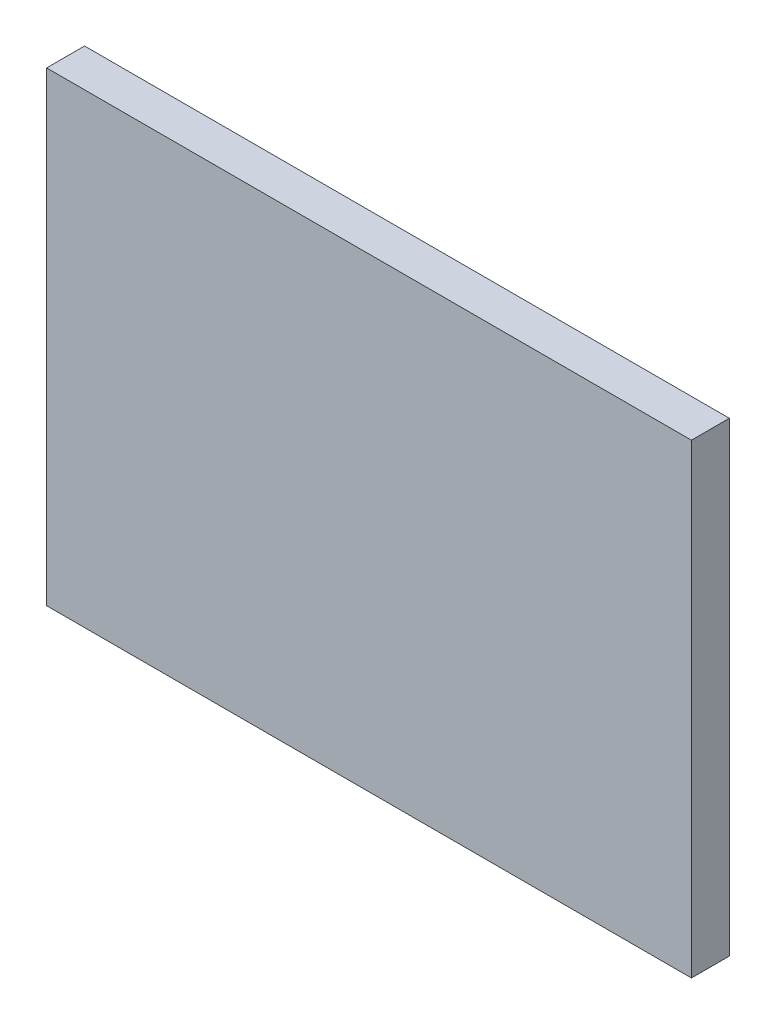
SolidWorks part; units mm, degrees
ref_plane "Front Plane" through (0, 0, 0) normal (0, 0, 1) x (1, 0, 0)
ref_plane "Top Plane" through (0, 0, 0) normal (0, 1, 0) x (1, 0, 0)
ref_plane "Right Plane" through (0, 0, 0) normal (1, 0, 0) x (0, 0, -1)
sketch "Sketch1" plane through (0, 0, 0) normal (0, 0, 1) x (1, 0, 0)
  line L1 (-53.975, 38.989) -> (53.975, 38.989)
  line L2 (-53.975, 38.989) -> (-53.975, -38.989)
  line L3 (-53.975, -38.989) -> (53.975, -38.989)
  line L4 (53.975, 38.989) -> (53.975, -38.989)
  line L5 (-53.975, 38.989) -> (53.975, -38.989) construction
  line L6 (-53.975, -38.989) -> (53.975, 38.989) construction
  point P0 (0, 0)
extrude "Boss-Extrude1" add sketch "Sketch1" along normal blind 6.35
